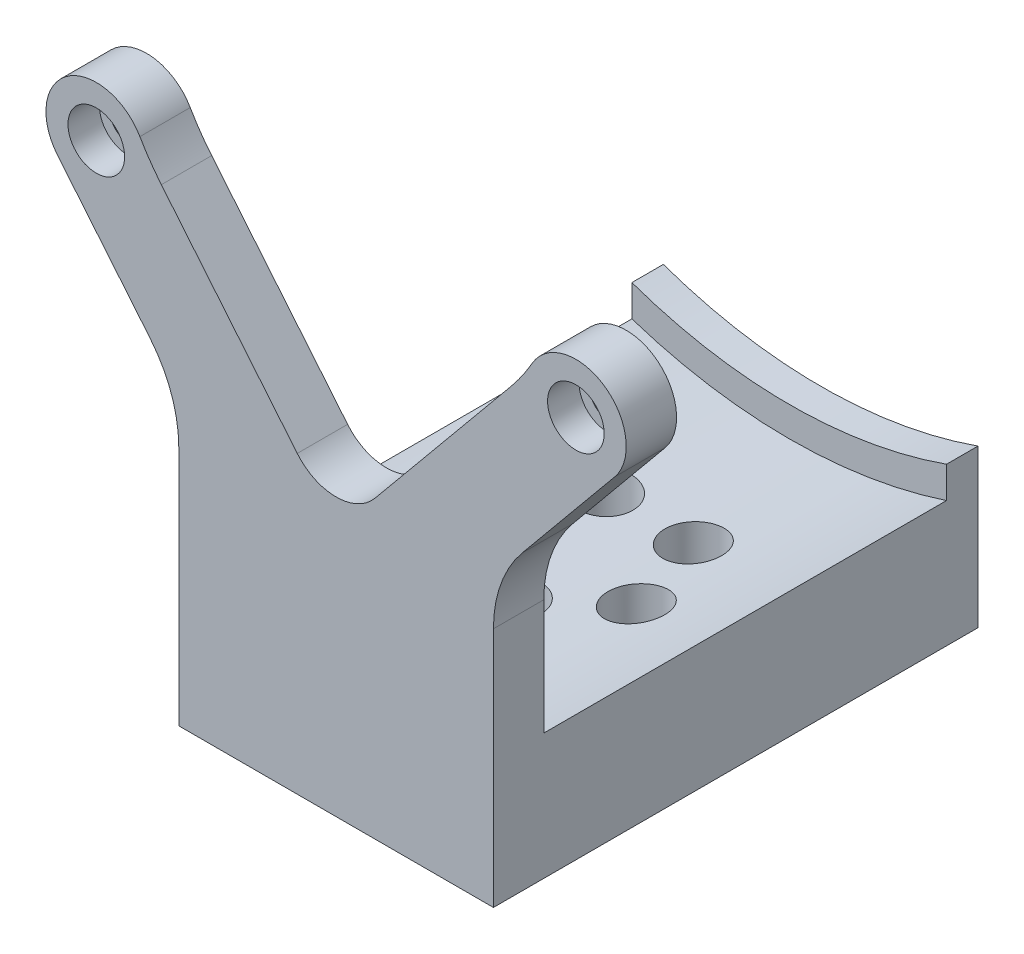
SolidWorks part; units mm, degrees
ref_plane "Front Plane" through (0, 0, 0) normal (0, 0, 1) x (1, 0, 0)
ref_plane "Top Plane" through (0, 0, 0) normal (0, 1, 0) x (1, 0, 0)
ref_plane "Right Plane" through (0, 0, 0) normal (1, 0, 0) x (0, 0, -1)
sketch "Sketch3" plane through (0, 0, 0) normal (0, 0, 1) x (1, 0, 0)
  line L0 (0, 0) -> (50, 0)
  line L1 (0, 0) -> (0, 20)
  line L2 (50, 0) -> (50, 20)
  arc A0 (0, 20) -> (50, 20) centre (25, 95.9934) ccw
  point P9 (25, 0)
  dimension "D2" = 80
  dimension "D1" = 50
  dimension "D3" = 20
extrude "Boss-Extrude1" add sketch "Sketch3" along normal blind 64
sketch "Sketch4" plane through (0, 0, 0) normal (0, 0, -1) x (-1, 0, 0)
  line L0 (-50, 0) -> (0, 0)
  line L1 (0, 0) -> (0, 25)
  line L3 (-50, 0) -> (-50, 25)
  arc A0 (-50, 25) -> (0, 25) centre (-25, 95.9934) ccw
  dimension "D1" = 25
extrude "Boss-Extrude2" add sketch "Sketch4" along normal blind 5
sketch "Sketch5" plane through (0, 0, 64) normal (0, 0, 1) x (1, 0, 0)
  line L0 (25, 95.9934) -> (25, 51.9934) construction
  line L1 (25, 95.9934) -> (-13.1051, 73.9934) construction
  line L2 (25, 95.9934) -> (63.1051, 73.9934) construction
  line L3 (0, 0) -> (50, 0)
  line L4 (0, 0) -> (0, 45.5362)
  line L5 (50, 0) -> (50, 45.5362)
  line L6 (-19.2762, 68.9025) -> (0, 45.5362)
  line L7 (69.2762, 68.9025) -> (50, 45.5362)
  line L8 (-2.77, 73.0843) -> (18.8289, 46.9025)
  line L9 (31.1711, 46.9025) -> (52.77, 73.0843)
  circle A0 centre (25, 95.9934) radius 44 construction
  circle A1 centre (63.1051, 73.9934) radius 2.75
  circle A2 centre (-13.1051, 73.9934) radius 2.75
  circle A3 centre (25, 95.9934) radius 36 construction
  arc A4 (69.2762, 68.9025) -> (56.1769, 77.9934) centre (63.1051, 73.9934) ccw
  arc A5 (-6.1769, 77.9934) -> (-19.2762, 68.9025) centre (-13.1051, 73.9934) ccw
  circle A6 centre (25, 51.9934) radius 2.75 construction
  circle A7 centre (25, 51.9934) radius 8 construction
  arc A8 (-6.1769, 77.9934) -> (-2.77, 73.0843) centre (25, 95.9934) ccw
  arc A9 (52.77, 73.0843) -> (56.1769, 77.9934) centre (25, 95.9934) ccw
  arc A10 (18.8289, 46.9025) -> (31.1711, 46.9025) centre (25, 51.9934) ccw
  point P15 (50, 0)
  point P16 (0, 45.5362)
  point P28 (-2.7745, 73.0898)
  dimension "D1" = 88
  dimension "D2" = 5.5
  dimension "D5" = 72
  dimension "D6" = 16
  dimension "D3" = 60
  dimension "D4" = 60
extrude "Boss-Extrude3" add sketch "Sketch5" along normal blind 8
sketch "Sketch6" plane through (0, 0, 72) normal (0, 0, 1) x (1, 0, 0)
  circle A0 centre (-13.1051, 73.9934) radius 4.5
  circle A1 centre (63.1051, 73.9934) radius 4.5
  dimension "D1" = 9
extrude "Cut-Extrude1" cut sketch "Sketch6" against normal blind 5
sketch "Sketch7" plane through (0, 0, 0) normal (0, -1, 0) x (1, 0, 0)
  line L0 (0, 72) -> (50, 72) construction
  line L1 (0, 64) -> (0, 0) construction
  circle A0 centre (25, 32) radius 12 construction
  circle A1 centre (25, 44) radius 2.75
  circle A2 centre (36.4127, 35.7082) radius 2.75
  circle A3 centre (32.0534, 22.2918) radius 2.75
  circle A4 centre (17.9466, 22.2918) radius 2.75
  circle A5 centre (13.5873, 35.7082) radius 2.75
  point P5 (25, 72)
  point P8 (0, 32)
  dimension "D1" = 24
  dimension "D2" = 5.5
  dimension "D3" = 5
extrude "Cut-Extrude2" cut sketch "Sketch7" against normal through all
ref_plane "Plane1" through (0, 20, 0) normal (0, 1, 0) x (1, 0, 0)
sketch "Sketch8" plane through (0, 20, 0) normal (0, 1, 0) x (1, 0, 0)
  circle A0 centre (25, -44) radius 4.5
  circle A1 centre (17.9466, -22.2918) radius 4.5
  circle A2 centre (32.0534, -22.2918) radius 4.5
  circle A3 centre (36.4127, -35.7082) radius 4.5
  circle A4 centre (13.5873, -35.7082) radius 4.5
  dimension "D1" = 9
extrude "Cut-Extrude3" cut sketch "Sketch8" against normal offset from surface (14 mm away) 6 up to face at (25, 0, 41.25)
fillet "Fillet2" radius 20 2 edges at (50, 45.5362, 68) (0, 45.5362, 68)
